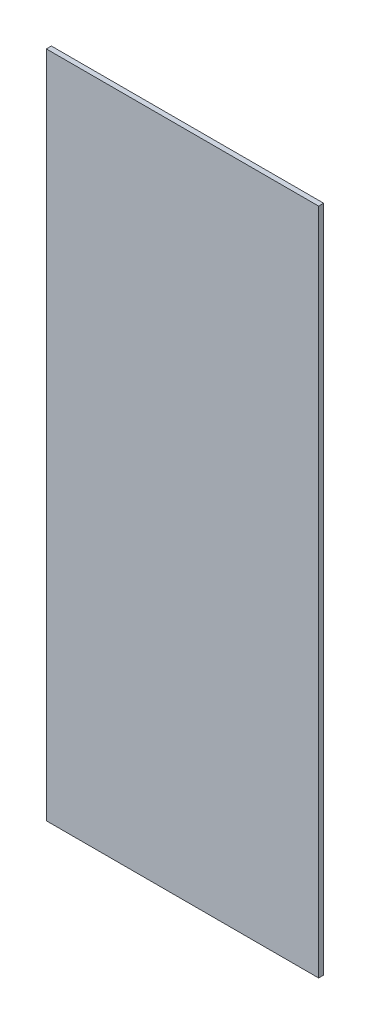
SolidWorks part; units mm, degrees
ref_plane "Front Plane" through (0, 0, 0) normal (0, 0, 1) x (1, 0, 0)
ref_plane "Top Plane" through (0, 0, 0) normal (0, 1, 0) x (1, 0, 0)
ref_plane "Right Plane" through (0, 0, 0) normal (1, 0, 0) x (0, 0, -1)
sketch "Sketch1" plane through (0, 0, 0) normal (0, 0, 1) x (1, 0, 0)
  line L1 (0, 0) -> (108.35, 0)
  line L2 (0, 0) -> (0, -266)
  line L3 (0, -266) -> (108.35, -266)
  line L4 (108.35, 0) -> (108.35, -266)
  dimension "D1" = 266
  dimension "D2" = 108.35
extrude "Boss-Extrude1" add sketch "Sketch1" along normal blind 2
